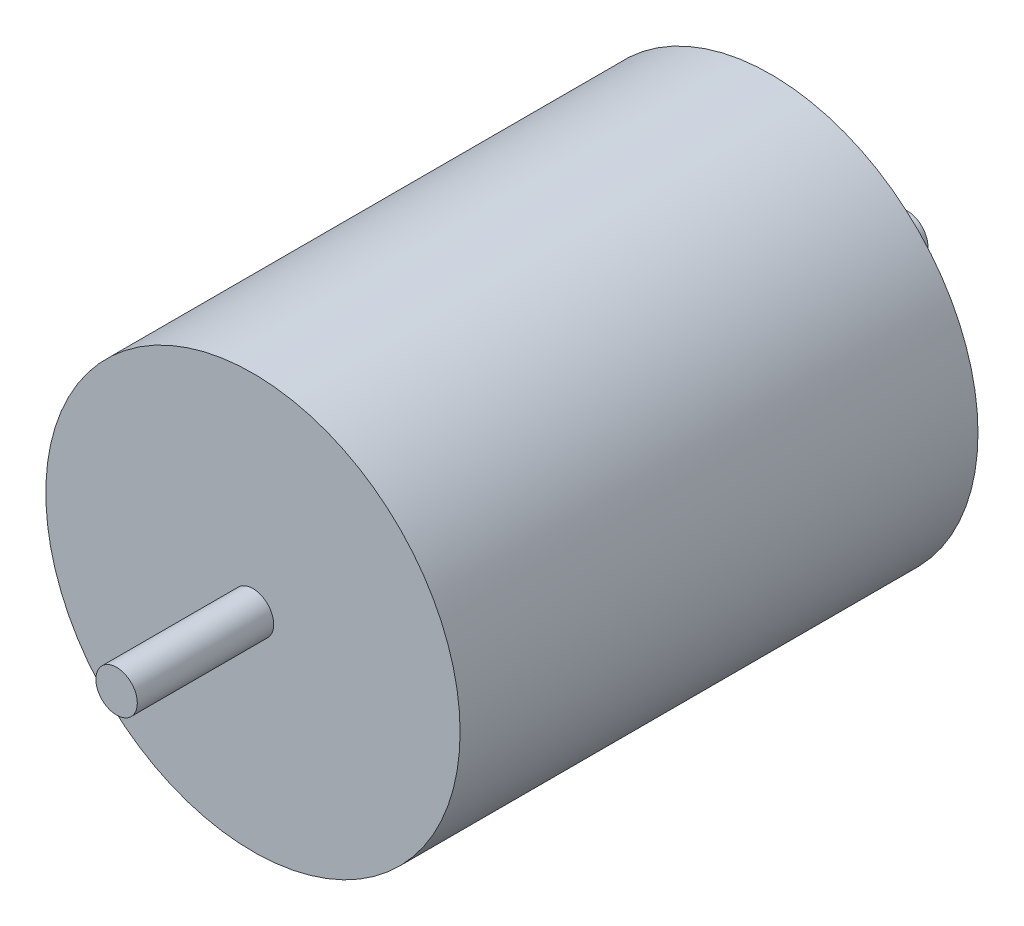
SolidWorks part; units mm, degrees
ref_plane "Front Plane" through (0, 0, 0) normal (0, 0, 1) x (1, 0, 0)
ref_plane "Top Plane" through (0, 0, 0) normal (0, 1, 0) x (1, 0, 0)
ref_plane "Right Plane" through (0, 0, 0) normal (1, 0, 0) x (0, 0, -1)
sketch "Sketch1" plane through (0, 0, 0) normal (0, 0, 1) x (1, 0, 0)
  circle A0 centre (0, 0) radius 0.6
  circle A1 centre (0, 0) radius 6
  dimension "D1" = 1.2
  dimension "D2" = 12
extrude "Boss-Extrude1" add sketch "Sketch1" along normal mid plane 15
extrude "Boss-Extrude2" add sketch "Sketch1<2>" along normal mid plane 22.9 contours A0
sketch "Sketch1<2>" plane through (0, 0, 0) normal (0, 0, 1) x (1, 0, 0) same geometry as "Sketch1"
